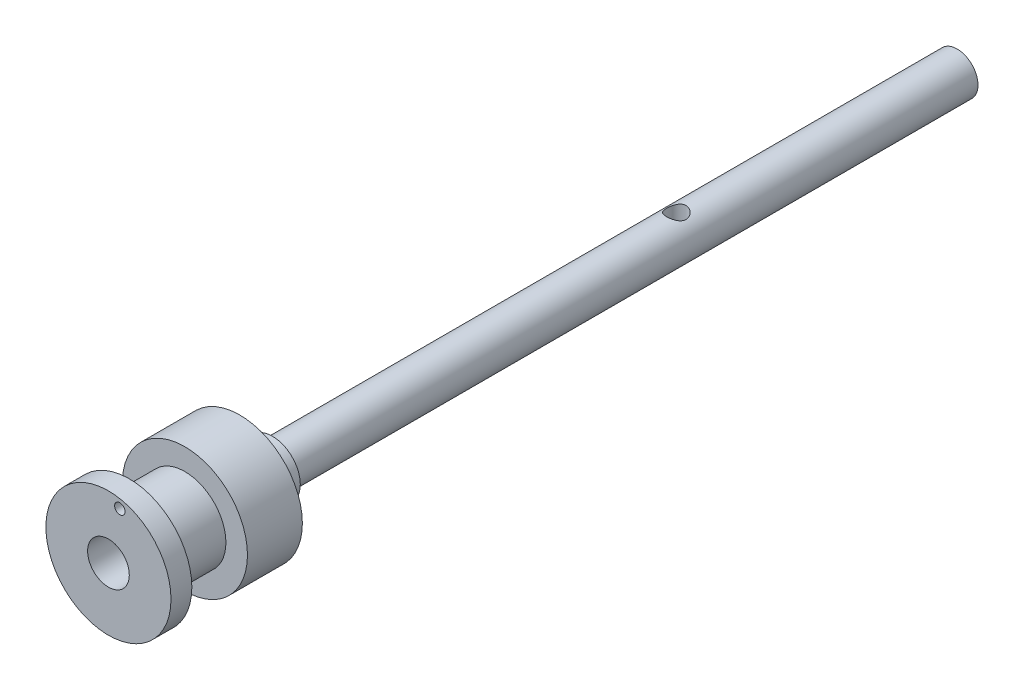
SolidWorks part; units mm, degrees
material "1060 Alloy"
ref_plane "Front Plane" through (0, 0, 0) normal (0, 0, 1) x (1, 0, 0)
ref_plane "Top Plane" through (0, 0, 0) normal (0, 1, 0) x (1, 0, 0)
ref_plane "Right Plane" through (0, 0, 0) normal (1, 0, 0) x (0, 0, -1)
sketch "Sketch1" plane through (0, 0, 0) normal (0, 0, 1) x (1, 0, 0)
  circle A0 centre (0, 0) radius 3
  dimension "D1" = 6
extrude "Boss-Extrude1" add sketch "Sketch1" along normal blind 98.5
sketch "Sketch2" plane through (0, 0, 98.5) normal (0, 0, 1) x (1, 0, 0)
  circle A0 centre (0, 0) radius 4
  dimension "D1" = 8
extrude "Boss-Extrude2" add sketch "Sketch2" along normal blind 4.7
sketch "Sketch3" plane through (0, 0, 103.2) normal (0, 0, 1) x (1, 0, 0)
  circle A0 centre (0, 0) radius 9
  dimension "D1" = 18
extrude "Boss-Extrude3" add sketch "Sketch3" along normal blind 7.9
sketch "Sketch4" plane through (0, 0, 111.1) normal (0, 0, 1) x (1, 0, 0)
  circle A0 centre (0, 0) radius 5.9
  dimension "D1" = 11.8
extrude "Boss-Extrude4" add sketch "Sketch4" along normal blind 8
sketch "Sketch5" plane through (0, 0, 119.1) normal (0, 0, 1) x (1, 0, 0)
  circle A0 centre (0, 0) radius 9
  dimension "D1" = 18
extrude "Boss-Extrude5" add sketch "Sketch5" along normal blind 3
sketch "Sketch6" plane through (0, 0, 0) normal (0, 1, 0) x (1, 0, 0)
  line L0 (0, 0) -> (0, -40.4) construction
  circle A0 centre (0, -40.4) radius 1.4
  dimension "D2" = 2.8
  dimension "D1" = 40.4
extrude "Cut-Extrude1" cut sketch "Sketch6" against normal blind 82 and the other way blind 82
sketch "Sketch7" plane through (0, 0, 122.1) normal (0, 0, 1) x (1, 0, 0)
  circle A0 centre (0, 0) radius 3
  circle A1 centre (1.6378, 7.5882) radius 0.75
  dimension "D1" = 6
  dimension "D2" = 1.5
extrude "Cut-Extrude2" cut sketch "Sketch7" against normal blind 9
